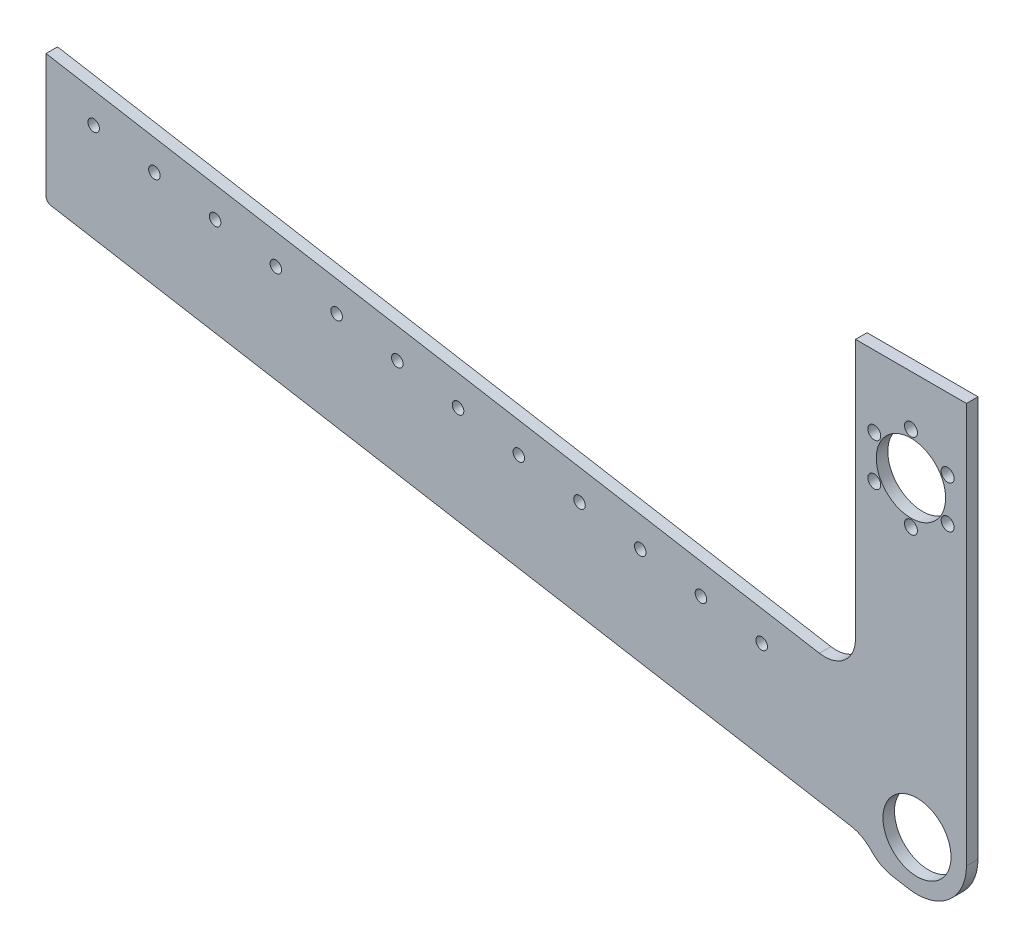
SolidWorks part; units mm, degrees
material "Polypropylene"
ref_plane "Front Plane" through (0, 0, 0) normal (0, 0, 1) x (1, 0, 0)
ref_plane "Top Plane" through (0, 0, 0) normal (0, 1, 0) x (1, 0, 0)
ref_plane "Right Plane" through (0, 0, 0) normal (1, 0, 0) x (0, 0, -1)
sketch "Sketch1" plane through (0, 0, 0) normal (0, 0, 1) x (1, 0, 0)
  line L0 (19.05, 0) -> (19.05, -76.2) construction
  line L1 (0, 19.05) -> (-57.15, 19.05) construction
  line L2 (19.05, -155.575) -> (168.9894, -155.575) construction
  line L3 (0, -95.25) -> (-57.15, -95.25) construction
  line L4 (-57.15, -95.25) -> (-57.15, 19.05) construction
  line L5 (168.9894, 7.239) -> (168.9894, -18.161) construction
  line L6 (168.9894, -18.161) -> (168.9894, -155.575) construction
  line L7 (168.9894, 7.239) -> (143.6189, 6.0141) construction
  line L8 (143.6189, 6.0141) -> (19.05, 0) construction
  line L9 (165.5424, -12.8509) -> (158.8645, -11.7052)
  line L12 (197.5644, 110.4886) -> (197.5644, -33.1911) construction
  line L16 (-190.0553, 107.5461) -> (-190.0553, 56.7461)
  line L17 (-190.0553, 107.5461) -> (128.7712, 52.8423)
  line L23 (-187.9448, 54.2427) -> (141.5847, -2.2975)
  line L24 (143.6189, 65.3594) -> (143.6189, 172.339)
  line L25 (143.6189, 172.339) -> (189.3729, 172.339)
  line L50 (189.3729, 172.339) -> (189.3729, 7.239)
  line L51 (166.4959, 172.339) -> (166.4959, 134.239) construction
  arc A0 (19.05, 0) -> (0, 19.05) centre (0, 0) ccw construction
  arc A1 (19.05, -76.2) -> (0, -95.25) centre (0, -76.2) cw construction
  circle A2 centre (168.9894, 7.239) radius 14.0335
  arc A3 (168.9894, -18.161) -> (143.6189, 6.0141) centre (168.9894, 7.239) ccw construction
  arc A4 (165.5424, -12.8509) -> (189.3729, 7.239) centre (168.9894, 7.239) ccw
  circle A15 centre (104.9708, 44.4781) radius 2.3812
  circle A16 centre (79.9366, 48.7734) radius 2.3813
  circle A17 centre (54.9024, 53.0687) radius 2.3812
  circle A18 centre (29.8682, 57.3641) radius 2.3812
  circle A19 centre (4.8341, 61.6594) radius 2.3813
  circle A20 centre (-20.2001, 65.9547) radius 2.3813
  circle A21 centre (-45.2343, 70.2501) radius 2.3813
  circle A22 centre (-70.2685, 74.5454) radius 2.3813
  arc A31 (-187.9448, 54.2427) -> (-190.0553, 56.7461) centre (-187.5153, 56.7461) cw
  arc A34 (158.8645, -11.7052) -> (150.2246, -7.0013) centre (161.4417, 3.3154) cw
  arc A48 (141.5847, -2.2975) -> (150.2246, -7.0013) centre (139.0075, -17.318) cw
  arc A101 (128.7712, 52.8423) -> (143.6189, 65.3594) centre (130.9189, 65.3594) ccw
  circle A102 centre (-170.4052, 91.7267) radius 2.3812
  circle A103 centre (-145.371, 87.4314) radius 2.3812
  circle A104 centre (-120.3368, 83.1361) radius 2.3813
  circle A105 centre (-95.3027, 78.8407) radius 2.3812
  circle A106 centre (166.4959, 134.239) radius 14.2875
  circle A107 centre (166.4959, 134.239) radius 17.4625 construction
  circle A108 centre (166.4959, 151.7015) radius 2.667
  circle A110 centre (166.4959, 134.239) radius 17.4625 construction
  circle A111 centre (181.6188, 142.9703) radius 2.667
  circle A112 centre (166.4959, 134.239) radius 17.4625 construction
  circle A114 centre (166.4959, 134.239) radius 17.4625 construction
  circle A115 centre (181.6188, 125.5078) radius 2.667
  circle A116 centre (166.4959, 134.239) radius 17.4625 construction
  circle A118 centre (166.4959, 134.239) radius 17.4625 construction
  circle A119 centre (166.4959, 116.7765) radius 2.667
  circle A120 centre (166.4959, 134.239) radius 17.4625 construction
  circle A122 centre (166.4959, 134.239) radius 17.4625 construction
  circle A123 centre (151.3729, 125.5077) radius 2.667
  circle A124 centre (166.4959, 134.239) radius 17.4625 construction
  circle A126 centre (166.4959, 134.239) radius 17.4625 construction
  circle A127 centre (151.3729, 142.9702) radius 2.667
  circle A128 centre (166.4959, 134.239) radius 17.4625 construction
  circle A130 centre (166.4959, 134.239) radius 17.4625 construction
  circle A131 centre (149.0334, 134.239) radius 2.667 [skipped]
  circle A132 centre (157.7646, 119.116) radius 2.667 [skipped]
  circle A133 centre (175.2271, 119.116) radius 2.667 [skipped]
  circle A134 centre (183.9584, 134.239) radius 2.667 [skipped]
  circle A135 centre (175.2271, 149.362) radius 2.667 [skipped]
  circle A136 centre (157.7646, 149.362) radius 2.667 [skipped]
  point P51 (-190.0553, 48.162)
  point P92 (143.8191, 3.8303)
  point P95 (150.6057, -10.2881)
  point P107 (-190.0576, 105.312)
  point P111 (166.4959, 134.239)
  dimension "D1" = 19.05
  dimension "D4" = 19.05
  dimension "D6" = 28.067
  dimension "D7" = 50.8
  dimension "D10" = 6.35
  dimension "D13" = 28.575
  dimension "D15" = 165.1
  dimension "D26" = 2.54
  dimension "D27" = 15.24
  dimension "D14" = 12.7
  dimension "D16" = 12
  dimension "D2" = 155.575
  dimension "D3" = 76.2
  dimension "D5" = 114.3
  dimension "D8" = 137.414
  dimension "D9" = 124.714
  dimension "D11" = 12.5
  dimension "D12" = 50.8
  dimension "D40" = 17.2798
  dimension "D41" = 9.4076
extrude "Boss-Extrude1" add sketch "Sketch1" along normal blind 4.7625
sketch "Sketch2" plane through (0, 0, 4.7625) normal (0, 0, 1) x (1, 0, 0)
  line L0 (-188.8163, 48.0139) -> (-189.0331, 50.6154)
  line L1 (-189.2853, 50.8905) -> (-190.3098, 51.0663)
  line L2 (-190.6393, 50.891) -> (-191.7109, 48.5105)
  line L3 (-191.7701, 48.4563) -> (-191.7658, 48.4813) construction
  line L4 (-189.7976, 50.9784) -> (-190.2743, 48.1996) construction
  line L5 (-188.7743, 49.2566) -> (-191.3363, 49.6962) construction
  line L6 (158.8645, -11.7052) -> (165.5424, -12.8509) construction
  line L7 (-191.1886, 49.6708) -> (-191.441, 48.1996) construction
  line L8 (-188.922, 49.2819) -> (-189.1077, 48.1996) construction
  line L11 (-188.7786, 47.943) -> (-191.7701, 48.4563)
  line L13 (-188.7743, 47.968) -> (-188.3036, 47.8873)
  line L14 (-188.3036, 47.8873) -> (-188.3079, 47.8622)
  line L15 (-188.3079, 47.8622) -> (-188.7786, 47.943)
  line L16 (-188.7786, 47.943) -> (-188.7743, 47.968) construction
  line L17 (-192.2365, 48.5621) -> (-192.2408, 48.537)
  line L18 (-192.2408, 48.537) -> (-191.7701, 48.4563)
  line L19 (-191.7658, 48.4813) -> (-192.2365, 48.5621)
  line L21 (-190.0553, 107.5461) -> (-190.0553, 56.7461) construction
  arc A0 (-190.3098, 51.0663) -> (-190.6393, 50.891) centre (-190.3613, 50.7659) ccw
  arc A1 (-189.0331, 50.6154) -> (-189.2853, 50.8905) centre (-189.3369, 50.5901) ccw
  arc A2 (-191.7658, 48.4813) -> (-191.7109, 48.5105) centre (-191.7572, 48.5314) ccw
  arc A3 (-188.8163, 48.0139) -> (-188.7743, 47.968) centre (-188.7657, 48.0181) ccw
  point P6 (-190.0553, 49.4764)
  dimension "D1" = 0.0254
  dimension "Root_fillet" = 0.3048
  dimension "Break_rad" = 0.0508
  dimension "Gap_width" = 2.2997
  dimension "Dedendum" = 1.524
  dimension "Addendum_plus" = 1.2954
  dimension "Pressure_angle" = 14.5
  dimension "D2" = 0.4775
